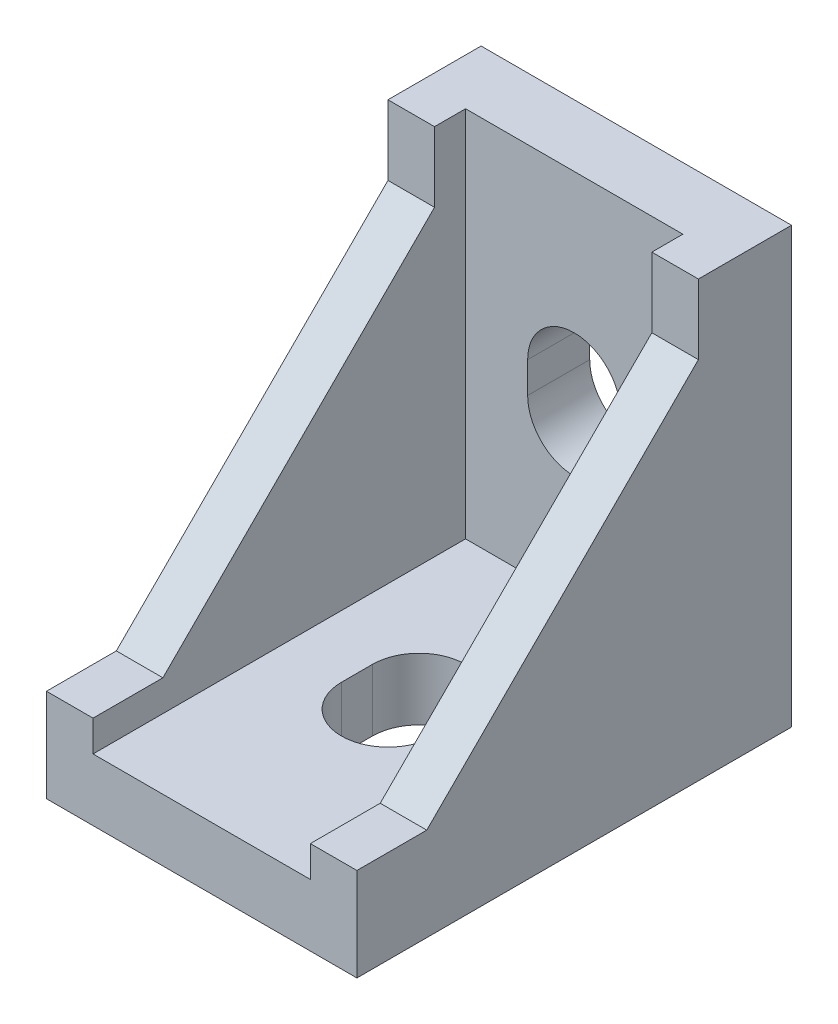
SolidWorks part; units mm, degrees
ref_plane "Front Plane" through (0, 0, 0) normal (0, 0, 1) x (1, 0, 0)
ref_plane "Top Plane" through (0, 0, 0) normal (0, 1, 0) x (1, 0, 0)
ref_plane "Right Plane" through (0, 0, 0) normal (1, 0, 0) x (0, 0, -1)
sketch "Sketch1" plane through (0, 0, 0) normal (0, 1, 0) x (1, 0, 0)
  line L1 (-10, -14) -> (10, -14)
  line L2 (-10, -14) -> (-10, 14)
  line L3 (-10, 14) -> (10, 14)
  line L4 (10, -14) -> (10, 14)
  line L5 (-10, -14) -> (10, 14) construction
  line L6 (-10, 14) -> (10, -14) construction
  point P0 (0, 0)
  dimension "D1" = 28
  dimension "D2" = 20
extrude "Boss-Extrude1" add sketch "Sketch1" along normal blind 4
sketch "Sketch3" plane through (0, 4, 0) normal (0, 1, 0) x (1, 0, 0)
  line L0 (0, -1000) -> (0, 49000) construction
  line L1 (0, 0) -> (0, -2) construction
  line L2 (3, 0) -> (3, -2)
  line L3 (-3, 0) -> (-3, -2)
  line L5 (10, 14) -> (-10, 14) construction
  arc A0 (3, 0) -> (-3, 0) centre (0, 0) ccw
  arc A1 (-3, -2) -> (3, -2) centre (0, -2) ccw
  point P5 (0, -1)
  dimension "D1" = 3
  dimension "D2" = 2
  dimension "D3" = 15
extrude "Cut-Extrude1" cut sketch "Sketch3" against normal through all
sketch "Sketch4" plane through (0, 0, 0) normal (0, -1, 0) x (1, 0, 0)
  line L0 (0, -1000) -> (0, 49000) construction
  line L1 (-10, 14) -> (10, 14) construction
  line L2 (-3, 10.1) -> (3, 10.1)
  line L3 (-3, 10.1) -> (-3, 12.1)
  line L4 (-3, 12.1) -> (3, 12.1)
  line L5 (3, 10.1) -> (3, 12.1)
  line L6 (-3, 10.1) -> (3, 12.1) construction
  line L7 (-3, 12.1) -> (3, 10.1) construction
  line L8 (-3, -12) -> (3, -12)
  line L9 (-3, -12) -> (-3, -10)
  line L10 (-3, -10) -> (3, -10)
  line L11 (3, -12) -> (3, -10)
  line L12 (-3, -12) -> (3, -10) construction
  line L13 (-3, -10) -> (3, -12) construction
  line L14 (10, -14) -> (-10, -14) construction
  point P1 (0, 11.1)
  point P8 (0, -11)
  dimension "D1" = 6
  dimension "D2" = 6
  dimension "D3" = 2
  dimension "D4" = 2
  dimension "D5" = 1.9
  dimension "D6" = 2
extrude "Boss-Extrude2" add sketch "Sketch4" along normal blind 1.25
ref_plane "Plane1" through (0, 7, -7) normal (0, -0.7071, 0.7071) x (1, 0, 0)
mirror "Mirror1" about plane through (0, 7, -7) normal (0, -0.7071, 0.7071) of "Boss-Extrude2", "Cut-Extrude1", "Boss-Extrude1"
sketch "Sketch5" plane through (10, 0, 0) normal (1, 0, 0) x (0, 0, -1)
  line L0 (-14, 4) -> (-14, 6)
  line L1 (-14, 6) -> (-9.5, 6)
  line L2 (-9.5, 6) -> (8, 23.5)
  line L3 (8, 23.5) -> (8, 28)
  line L4 (8, 28) -> (10, 28)
  line L5 (10, 28) -> (10, 4)
  line L6 (-0.7782, 14.7782) -> (14.7782, -0.7782) construction
  line L7 (10, 28) -> (10, 4) construction
  line L8 (10, 4) -> (-14, 4)
  dimension "D1" = 2
  dimension "D2" = 2
  dimension "D3" = 4.5
  dimension "D4" = 4.5
extrude "Boss-Extrude3" add sketch "Sketch5" against normal blind 3
mirror "Mirror2" about plane through (0, 0, 0) normal (1, 0, 0) of "Boss-Extrude3"
